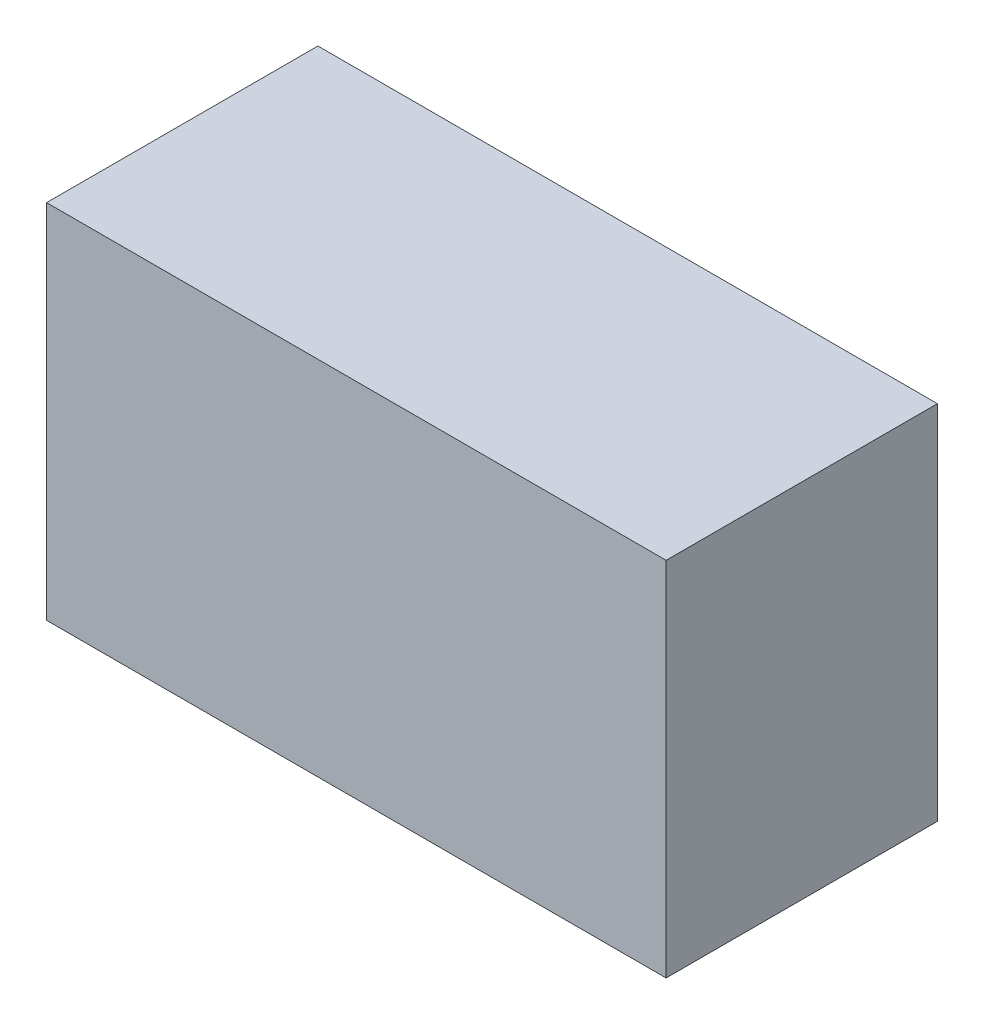
SolidWorks part; units mm, degrees
material "Polyurethane Foam Rigid"
ref_plane "X-Y Datum" through (0, 0, 0) normal (0, 0, 1) x (1, 0, 0)
ref_plane "X-Z Datum" through (0, 0, 0) normal (0, 1, 0) x (1, 0, 0)
ref_plane "Y-Z Datum" through (0, 0, 0) normal (1, 0, 0) x (0, 0, -1)
sketch "Sketch1" plane through (0, 0, 0) normal (0, 0, 1) x (1, 0, 0)
  line L1 (-43.5, -25.4) -> (43.5, -25.4)
  line L2 (-43.5, -25.4) -> (-43.5, 25.4)
  line L3 (-43.5, 25.4) -> (43.5, 25.4)
  line L4 (43.5, -25.4) -> (43.5, 25.4)
  line L5 (-43.5, -25.4) -> (43.5, 25.4) construction
  line L6 (-43.5, 25.4) -> (43.5, -25.4) construction
  point P0 (0, 0)
  dimension "D1" = 87.0001
  dimension "D2" = 50.8
extrude "Boss-Extrude1" add sketch "Sketch1" along normal blind 38.1
